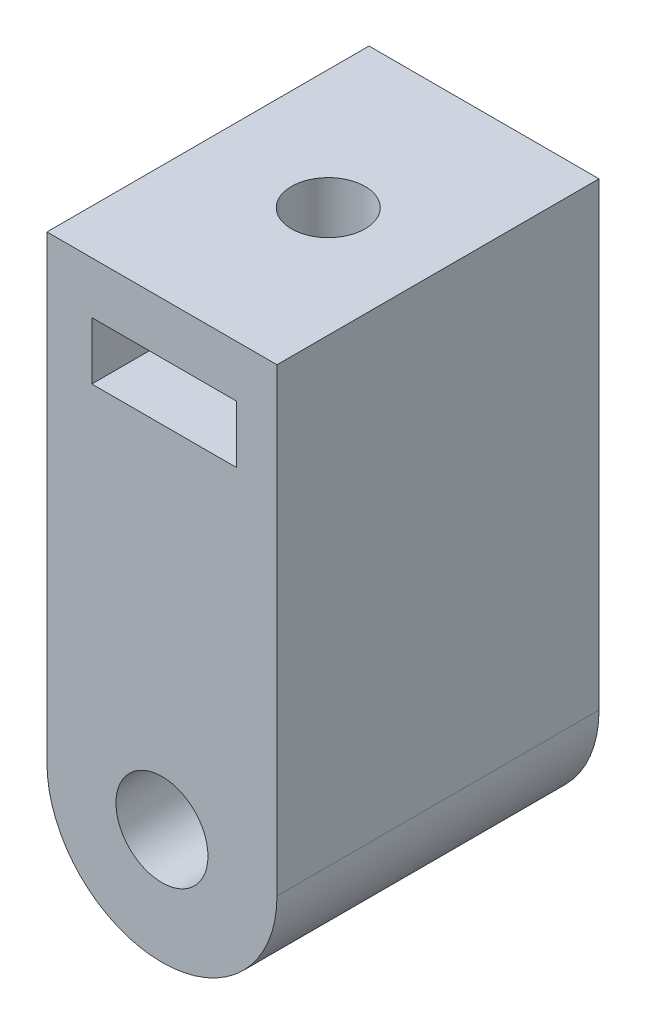
SolidWorks part; units mm, degrees
ref_plane "Спереди" through (0, 0, 0) normal (0, 0, 1) x (1, 0, 0)
ref_plane "Сверху" through (0, 0, 0) normal (0, 1, 0) x (1, 0, 0)
ref_plane "Справа" through (0, 0, 0) normal (1, 0, 0) x (0, 0, -1)
sketch "Эскиз1" plane through (0, 0, 0) normal (0, 0, 1) x (1, 0, 0)
  circle A0 centre (0, 0) radius 2
  circle A1 centre (0, 0) radius 5
extrude "Бобышка-Вытянуть1" add sketch "Эскиз1" along normal blind 14
sketch "Эскиз2" plane through (0, 0, 14) normal (0, 0, 1) x (1, 0, 0)
  line L0 (-5, 0) -> (-2, 0)
  line L2 (-5, 0) -> (-5, 20)
  line L3 (-5, 20) -> (5, 20)
  line L4 (5, 0) -> (5, 20)
  line L5 (0.4851, 1.9403) -> (5, 20) construction
  line L6 (-5, 20) -> (-0.4851, 1.9403) construction
  line L7 (2, 0) -> (5, 0)
  arc A0 (2, 0) -> (-2, 0) centre (0, 0) ccw
  point P0 (0, 0)
  point P9 (0, 0)
  point P12 (0, 0)
extrude "Бобышка-Вытянуть2" add sketch "Эскиз2" against normal up to surface (14 mm away) up to face at (5, 0, 0)
sketch "Эскиз5" plane through (0, 0, 14) normal (0, 0, 1) x (1, 0, 0)
  line L1 (3.25, 17.75) -> (-3.05, 17.75)
  line L2 (3.25, 17.75) -> (3.25, 15.25)
  line L3 (3.25, 15.25) -> (-3.05, 15.25)
  line L4 (-3.05, 17.75) -> (-3.05, 15.25)
  line L5 (3.25, 17.75) -> (-3.05, 15.25) construction
  line L6 (3.25, 15.25) -> (-3.05, 17.75) construction
  point P0 (0.1, 16.5)
  point P5 (0, 0)
  point P6 (0, 0)
  point P7 (0, 0)
extrude "Вырез-Вытянуть3" cut sketch "Эскиз5" against normal blind 10
sketch "Эскиз8" plane through (0, 15.25, 0) normal (0, 1, 0) x (1, 0, 0)
  line L0 (-3.05, -14) -> (-5.0865, -14)
sketch "Эскиз10" plane through (-5, 0, 0) normal (-1, 0, 0) x (0, 0, 1)
  line L0 (12.5, 3.2685) -> (14, 3.2685) construction
  line L1 (1.4417, 2.925) -> (12.5, 2.925)
  line L2 (1.4417, 2.925) -> (1.4417, 12.975)
  line L3 (1.4417, 12.975) -> (12.5, 12.975)
  line L4 (12.5, 2.925) -> (12.5, 12.975)
  line L5 (1.4417, 2.925) -> (12.5, 12.975) construction
  line L6 (1.4417, 12.975) -> (12.5, 2.925) construction
  line L7 (14, 20) -> (14, 0) construction
  line L8 (6.9709, 7.95) -> (12.5, 7.95) construction
  line L9 (6.9709, 2.925) -> (14, 2.925) construction
  line L10 (0, 0) -> (0, 20) construction
  point P0 (6.9709, 7.95)
  point P12 (0, 0)
  dimension "D1" = 1.4417
extrude "Вырез-Вытянуть5" cut sketch "Эскиз10" against normal blind 9.4
sketch "Эскиз12" plane through (0, 2.925, 0) normal (0, 1, 0) x (1, 0, 0)
  line L0 (0.1995, -1.4417) -> (0.1995, -12.5) construction
  line L1 (4.4, -1.4417) -> (-5, -1.4417) construction
  line L2 (4.4, -12.5) -> (-5, -12.5) construction
  line L3 (-5, -6.9709) -> (4.4, -6.9709) construction
  line L4 (-5, -1.4417) -> (-5, -12.5) construction
  line L5 (4.4, -1.4417) -> (4.4, -12.5) construction
  circle A0 centre (0.1995, -6.9709) radius 1.6
  point P14 (0, 0)
  point P15 (0, 0)
  point P16 (0, 0)
  point P17 (0, 0)
extrude "Вырез-Вытянуть7" cut sketch "Эскиз12" along normal through all
sketch "Эскиз13" plane through (0, 15.25, 0) normal (0, 1, 0) x (1, 0, 0)
  line L0 (-1.3858, -4.2257) -> (-1.3858, -4)
  line L1 (3.3695, -6.9706) -> (1.7842, -4.2254)
  line L2 (1.7842, -4.2254) -> (-1.3858, -4.2257)
  line L3 (-1.3858, -4.2257) -> (-2.9705, -6.9711)
  line L4 (-2.9705, -6.9711) -> (-1.3853, -9.7163)
  line L5 (-1.3853, -9.7163) -> (1.7847, -9.716)
  line L6 (1.7847, -9.716) -> (3.3695, -6.9706)
  line L7 (3.25, -4) -> (-3.05, -4) construction
  line L8 (3.3308, -6.9706) -> (3.3695, -6.9706)
  circle A0 centre (0.1995, -6.9709) radius 3.17 construction
